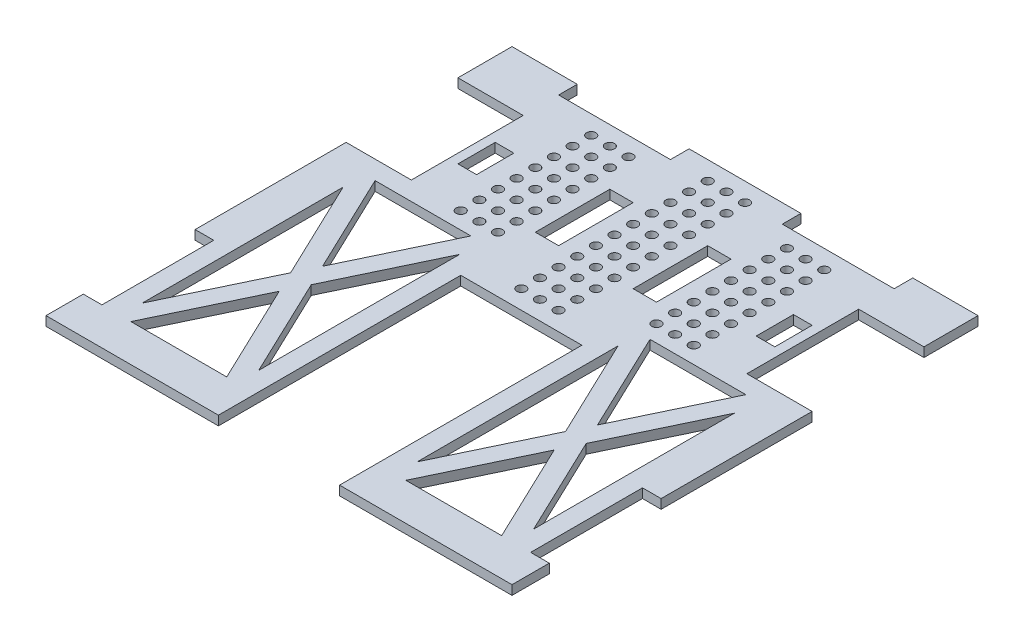
SolidWorks part; units mm, degrees
material "7050-T73510"
ref_plane "Front Plane" through (0, 0, 0) normal (0, 0, 1) x (1, 0, 0)
ref_plane "Top Plane" through (0, 0, 0) normal (0, 1, 0) x (1, 0, 0)
ref_plane "Right Plane" through (0, 0, 0) normal (1, 0, 0) x (0, 0, -1)
sketch "Sketch1" plane through (0, 0, 0) normal (0, 1, 0) x (1, 0, 0)
  line L0 (0, -55) -> (0, 55) construction
  line L1 (-158.75, -76.2) -> (158.75, -76.2)
  line L2 (-158.75, -76.2) -> (-158.75, 76.2)
  line L3 (-158.75, 76.2) -> (158.75, 76.2)
  line L4 (158.75, -76.2) -> (158.75, 76.2)
  line L5 (-158.75, -76.2) -> (158.75, 76.2) construction
  line L6 (-158.75, 76.2) -> (158.75, -76.2) construction
  line L7 (-158.75, -76.2) -> (-25.4, -76.2)
  line L8 (-158.75, -76.2) -> (-158.75, -241.3)
  line L9 (-158.75, -241.3) -> (-25.4, -241.3)
  line L10 (-25.4, -76.2) -> (-25.4, -241.3)
  line L11 (25.4, -76.2) -> (25.4, -241.3)
  line L12 (158.75, -241.3) -> (25.4, -241.3)
  line L13 (158.75, -76.2) -> (158.75, -241.3)
  line L14 (158.75, -76.2) -> (25.4, -76.2)
  line L15 (-41.275, -76.2) -> (-41.275, -241.3)
  line L16 (41.275, -76.2) -> (41.275, -241.3)
  point P0 (0, 0)
  dimension "D1" = 317.5
  dimension "D2" = 152.4
  dimension "D3" = 317.5
  dimension "D4" = 50.8
  dimension "D5" = 15.875
extrude "Boss-Extrude1" add sketch "Sketch1" along normal blind 6.35 contours L15 L1 L8 L9 | L14 L16 L12 L13 | L1 L7 L14 L4 L3 L2 region at (0, 0, 0) region at (-100.0125, 0, 158.75) region at (100.0125, 0, 158.75)
sketch "Sketch2" plane through (0, 6.35, 0) normal (0, 1, 0) x (1, 0, 0)
  line L0 (158.75, -241.3) -> (158.75, 76.2) construction
  line L1 (158.75, 39.37) -> (114.3, 39.37)
  line L2 (158.75, 39.37) -> (158.75, -36.83)
  line L3 (158.75, -36.83) -> (114.3, -36.83)
  line L4 (114.3, 39.37) -> (114.3, -36.83)
  line L5 (-158.75, 76.2) -> (158.75, 76.2) construction
  line L6 (158.75, -139.7) -> (146.05, -139.7)
  line L7 (158.75, -139.7) -> (158.75, -215.9)
  line L8 (158.75, -215.9) -> (146.05, -215.9)
  line L9 (146.05, -139.7) -> (146.05, -215.9)
  line L10 (0, -3.4925) -> (0, 3.4925) construction
  line L11 (-158.75, -215.9) -> (-146.05, -215.9)
  line L12 (-146.05, -139.7) -> (-146.05, -215.9)
  line L13 (-158.75, -139.7) -> (-146.05, -139.7)
  line L14 (-158.75, -139.7) -> (-158.75, -215.9)
  line L15 (-158.75, -36.83) -> (-114.3, -36.83)
  line L16 (-114.3, 39.37) -> (-114.3, -36.83)
  line L17 (-158.75, 39.37) -> (-114.3, 39.37)
  line L18 (-158.75, 39.37) -> (-158.75, -36.83)
  line L19 (-114.3, 63.5) -> (-38.1, 63.5)
  line L20 (114.3, 76.2) -> (38.1, 76.2)
  line L21 (114.3, 76.2) -> (114.3, 63.5)
  line L22 (114.3, 63.5) -> (38.1, 63.5)
  line L23 (38.1, 76.2) -> (38.1, 63.5)
  line L24 (-38.1, 76.2) -> (-38.1, 63.5)
  line L25 (-114.3, 76.2) -> (-38.1, 76.2)
  line L26 (-114.3, 76.2) -> (-114.3, 63.5)
  dimension "D1" = 44.45
  dimension "D2" = 12.7
  dimension "D3" = 76.2
  dimension "D4" = 76.2
  dimension "D5" = 36.83
  dimension "D6" = 215.9
  dimension "D7" = 76.2
  dimension "D8" = 12.7
  dimension "D9" = 76.2
extrude "Cut-Extrude1" cut sketch "Sketch2" against normal through all
sketch "Sketch4" plane through (0, 6.35, 0) normal (0, 1, 0) x (1, 0, 0)
  line L0 (41.275, -76.2) -> (41.275, -241.3) construction
  line L1 (53.975, -215.9) -> (133.35, -215.9)
  line L2 (53.975, -215.9) -> (53.975, -49.53)
  line L3 (53.975, -49.53) -> (133.35, -49.53)
  line L4 (133.35, -215.9) -> (133.35, -49.53)
  line L5 (146.05, -139.7) -> (146.05, -215.9) construction
  line L6 (158.75, -241.3) -> (41.275, -241.3) construction
  line L7 (53.975, -215.9) -> (133.35, -49.53) construction
  line L8 (53.975, -49.53) -> (133.35, -215.9) construction
  line L9 (133.35, -201.1532) -> (61.0107, -49.53)
  line L10 (126.3143, -215.9) -> (53.975, -64.2768)
  line L11 (53.975, -201.1532) -> (126.3143, -49.53)
  line L12 (61.0107, -215.9) -> (133.35, -64.2768)
  line L13 (114.3, -36.83) -> (158.75, -36.83) construction
  line L14 (0, -3.4925) -> (0, 3.4925) construction
  line L15 (-53.975, -201.1532) -> (-126.3143, -49.53)
  line L16 (-126.3143, -215.9) -> (-53.975, -64.2768)
  line L17 (-133.35, -201.1532) -> (-61.0107, -49.53)
  line L18 (-61.0107, -215.9) -> (-133.35, -64.2768)
  line L19 (-53.975, -49.53) -> (-133.35, -49.53)
  line L20 (-133.35, -215.9) -> (-133.35, -49.53)
  line L21 (-53.975, -215.9) -> (-133.35, -215.9)
  line L22 (-53.975, -215.9) -> (-53.975, -49.53)
  point P18 (116.9135, -166.7022)
  dimension "D1" = 12.7
  dimension "D2" = 12.7
  dimension "D3" = 25.4
  dimension "D4" = 12.7
  dimension "D5" = 12.7
extrude "Cut-Extrude3" cut sketch "Sketch4" against normal through all contours L12 L9 L4 | L12 L1 L10 | L2 L11 L10 | L9 L11 L3 | L21 L18 L16 | L20 L17 L18 | L17 L19 L15 | L15 L22 L16 region at (93.6625, 6.35, 193.0873) region at (64.8589, 6.35, 132.715) region at (122.4661, 6.35, 132.715) region at (93.6625, 6.35, 72.3427) region at (-64.8589, 6.35, 132.715) region at (-93.6625, 6.35, 72.3427) region at (-93.6625, 6.35, 193.0873) region at (-122.4661, 6.35, 132.715)
sketch "Sketch3" plane through (0, 6.35, 0) normal (0, 1, 0) x (1, 0, 0)
  line L0 (-41.275, -76.2) -> (41.275, -76.2) construction
  line L1 (-41.275, -25.4) -> (-25.4, -25.4)
  line L2 (-41.275, -25.4) -> (-41.275, 25.4)
  line L3 (-41.275, 25.4) -> (-25.4, 25.4)
  line L4 (-25.4, -25.4) -> (-25.4, 25.4)
  line L5 (0, -3.4925) -> (0, 3.4925) construction
  line L6 (41.275, 25.4) -> (25.4, 25.4)
  line L7 (25.4, -25.4) -> (25.4, 25.4)
  line L8 (41.275, -25.4) -> (25.4, -25.4)
  line L9 (41.275, -25.4) -> (41.275, 25.4)
  line L10 (114.3, 39.37) -> (114.3, -36.83) construction
  line L11 (95.25, 13.97) -> (107.95, 13.97)
  line L12 (95.25, 13.97) -> (95.25, -11.43)
  line L13 (95.25, -11.43) -> (107.95, -11.43)
  line L14 (107.95, 13.97) -> (107.95, -11.43)
  line L15 (38.1, 63.5) -> (114.3, 63.5) construction
  line L16 (-95.25, -11.43) -> (-107.95, -11.43)
  line L17 (-107.95, 13.97) -> (-107.95, -11.43)
  line L18 (-95.25, 13.97) -> (-107.95, 13.97)
  line L19 (-95.25, 13.97) -> (-95.25, -11.43)
  dimension "D1" = 50.8
  dimension "D2" = 15.875
  dimension "D3" = 50.8
  dimension "D4" = 50.8
  dimension "D5" = 25.4
  dimension "D6" = 12.7
  dimension "D7" = 6.35
  dimension "D8" = 49.53
extrude "Cut-Extrude2" cut sketch "Sketch3" against normal through all
sketch "Sketch5" plane through (0, 6.35, 0) normal (0, 1, 0) x (1, 0, 0)
  line L0 (0, -3.4925) -> (0, 3.4925) construction
  line L2 (-38.1, 76.2) -> (38.1, 76.2) construction
  line L3 (41.275, -25.4) -> (41.275, 25.4) construction
  line L4 (114.3, 63.5) -> (38.1, 63.5) construction
  circle A0 centre (12.7, 63.5) radius 3.175
  circle A1 centre (12.7, 50.8) radius 3.175
  circle A2 centre (12.7, 38.1) radius 3.175
  circle A3 centre (12.7, 25.4) radius 3.175
  circle A4 centre (12.7, 12.7) radius 3.175
  circle A5 centre (12.7, 0) radius 3.175
  circle A6 centre (12.7, -12.7) radius 3.175
  circle A7 centre (12.7, -25.4) radius 3.175
  circle A8 centre (12.7, -38.1) radius 3.175
  circle A9 centre (12.7, -50.8) radius 3.175
  circle A10 centre (12.7, -63.5) radius 3.175
  circle A11 centre (0, 50.8) radius 3.175
  circle A12 centre (0, 38.1) radius 3.175
  circle A13 centre (0, 25.4) radius 3.175
  circle A14 centre (0, 12.7) radius 3.175
  circle A15 centre (0, 0) radius 3.175
  circle A16 centre (0, -12.7) radius 3.175
  circle A17 centre (0, -25.4) radius 3.175
  circle A18 centre (0, -38.1) radius 3.175
  circle A19 centre (0, -50.8) radius 3.175
  circle A20 centre (0, -63.5) radius 3.175
  circle A21 centre (-12.7, 50.8) radius 3.175
  circle A22 centre (-12.7, 38.1) radius 3.175
  circle A23 centre (-12.7, 25.4) radius 3.175
  circle A24 centre (-12.7, 12.7) radius 3.175
  circle A25 centre (-12.7, 0) radius 3.175
  circle A26 centre (-12.7, -12.7) radius 3.175
  circle A27 centre (-12.7, -25.4) radius 3.175
  circle A28 centre (-12.7, -38.1) radius 3.175
  circle A29 centre (-12.7, -50.8) radius 3.175
  circle A30 centre (-12.7, -63.5) radius 3.175
  circle A31 centre (0, 63.5) radius 3.175
  circle A32 centre (-12.7, 63.5) radius 3.175
  circle A33 centre (53.975, 50.8) radius 3.175
  circle A34 centre (66.675, 50.8) radius 3.175
  circle A35 centre (79.375, 50.8) radius 3.175
  circle A36 centre (66.675, 38.1) radius 3.175
  circle A37 centre (79.375, 38.1) radius 3.175
  circle A38 centre (66.675, 25.4) radius 3.175
  circle A39 centre (79.375, 25.4) radius 3.175
  circle A40 centre (66.675, 12.7) radius 3.175
  circle A41 centre (79.375, 12.7) radius 3.175
  circle A42 centre (66.675, 0) radius 3.175
  circle A43 centre (79.375, 0) radius 3.175
  circle A44 centre (66.675, -12.7) radius 3.175
  circle A45 centre (79.375, -12.7) radius 3.175
  circle A46 centre (66.675, -25.4) radius 3.175
  circle A47 centre (79.375, -25.4) radius 3.175
  circle A48 centre (66.675, -38.1) radius 3.175
  circle A49 centre (79.375, -38.1) radius 3.175
  circle A50 centre (53.975, 38.1) radius 3.175
  circle A51 centre (53.975, 25.4) radius 3.175
  circle A52 centre (53.975, 12.7) radius 3.175
  circle A53 centre (53.975, 0) radius 3.175
  circle A54 centre (53.975, -12.7) radius 3.175
  circle A55 centre (53.975, -25.4) radius 3.175
  circle A56 centre (53.975, -38.1) radius 3.175
  circle A57 centre (-53.975, -38.1) radius 3.175
  circle A58 centre (-53.975, -25.4) radius 3.175
  circle A59 centre (-53.975, -12.7) radius 3.175
  circle A60 centre (-53.975, 0) radius 3.175
  circle A61 centre (-53.975, 12.7) radius 3.175
  circle A62 centre (-53.975, 25.4) radius 3.175
  circle A63 centre (-53.975, 38.1) radius 3.175
  circle A64 centre (-79.375, -38.1) radius 3.175
  circle A65 centre (-66.675, -38.1) radius 3.175
  circle A66 centre (-79.375, -25.4) radius 3.175
  circle A67 centre (-66.675, -25.4) radius 3.175
  circle A68 centre (-79.375, -12.7) radius 3.175
  circle A69 centre (-66.675, -12.7) radius 3.175
  circle A70 centre (-79.375, 0) radius 3.175
  circle A71 centre (-66.675, 0) radius 3.175
  circle A72 centre (-79.375, 12.7) radius 3.175
  circle A73 centre (-66.675, 12.7) radius 3.175
  circle A74 centre (-79.375, 25.4) radius 3.175
  circle A75 centre (-66.675, 25.4) radius 3.175
  circle A76 centre (-79.375, 38.1) radius 3.175
  circle A77 centre (-66.675, 38.1) radius 3.175
  circle A78 centre (-79.375, 50.8) radius 3.175
  circle A79 centre (-66.675, 50.8) radius 3.175
  circle A80 centre (-53.975, 50.8) radius 3.175
  dimension "D1" = 6.35
  dimension "D6" = 6.35
  dimension "D2" = 12.7
  dimension "D3" = 12.7
  dimension "D7" = 12.7
  dimension "D8" = 12.7
  dimension "D4" = 11
  dimension "D5" = 3
  dimension "D9" = 3
  dimension "D10" = 8
extrude "Cut-Extrude4" cut sketch "Sketch5" against normal through all
